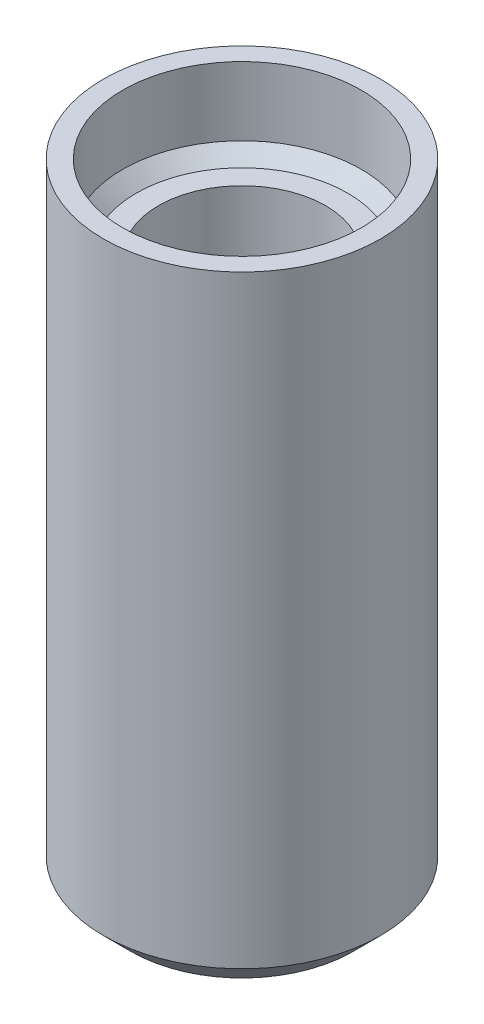
SolidWorks part; units mm, degrees
ref_plane "Front Plane" through (0, 0, 0) normal (0, 0, 1) x (1, 0, 0)
ref_plane "Top Plane" through (0, 0, 0) normal (0, 1, 0) x (1, 0, 0)
ref_plane "Right Plane" through (0, 0, 0) normal (1, 0, 0) x (0, 0, -1)
sketch "Sketch1" plane through (0, 0, 0) normal (0, 1, 0) x (1, 0, 0)
  line L0 (-2.5652, -1.65) -> (2.5652, -1.65)
  circle A0 centre (0, 0) radius 3.05
  circle A1 centre (0, 0) radius 5.05
  dimension "D1" = 6.1
  dimension "D3" = 1.65
  dimension "D2" = 2
extrude "Boss-Extrude1" add sketch "Sketch1" along normal blind 20 contours A1 A0 | L0 A0 region at (0, 0, 2.2227) region at (-4.9072, 0, 0)
sketch "Sketch2" plane through (0, 0, 0) normal (0, -1, 0) x (1, 0, 0)
  circle A1 centre (0, 0) radius 5.05
  circle A2 centre (0, 0) radius 5.05
  dimension "D1" = 0
extrude "Boss-Extrude2" add sketch "Sketch2" against normal blind 2
sketch "Sketch4" plane through (0, 20, 0) normal (0, 1, 0) x (1, 0, 0)
  circle A0 centre (0, 0) radius 4.35
  circle A1 centre (0, 0) radius 5.05
  circle A2 centre (0, 0) radius 5.05
  dimension "D1" = 0
  dimension "D2" = 0.7
extrude "Boss-Extrude3" add sketch "Sketch4" along normal blind 3
chamfer "Chamfer1" distance 1 angle 45 1 edges at (0, 0, 5.05)
chamfer "Chamfer2" distance 0.5 angle 45 1 edges at (0, 20, 4.35)
sketch "Sketch5" plane through (0, 0, 0) normal (0, -1, 0) x (1, 0, 0)
  line L0 (-1.326, 0) -> (1.326, 0) construction
  line L1 (-3.5217, -2) -> (3.5217, -2) construction
  circle A0 centre (0, 0) radius 4.05 construction
  text T0 "<b>3</b>" font "Calibri" height in points 16
  dimension "D1" = 2
extrude "Cut-Extrude1" cut sketch "Sketch5" against normal blind 0.4
extrude "Boss-Extrude4" add sketch "Sketch5<2>" against normal blind 0.4 separate body
sketch "Sketch5<2>" plane through (0, 0, 0) normal (0, -1, 0) x (1, 0, 0) same geometry as "Sketch5"
equation "\"ID\"= 6.3"
equation "\"notch\"= 6.3 / 2 - 1.5"
equation "\"D3@Sketch1\"=\"notch\""
